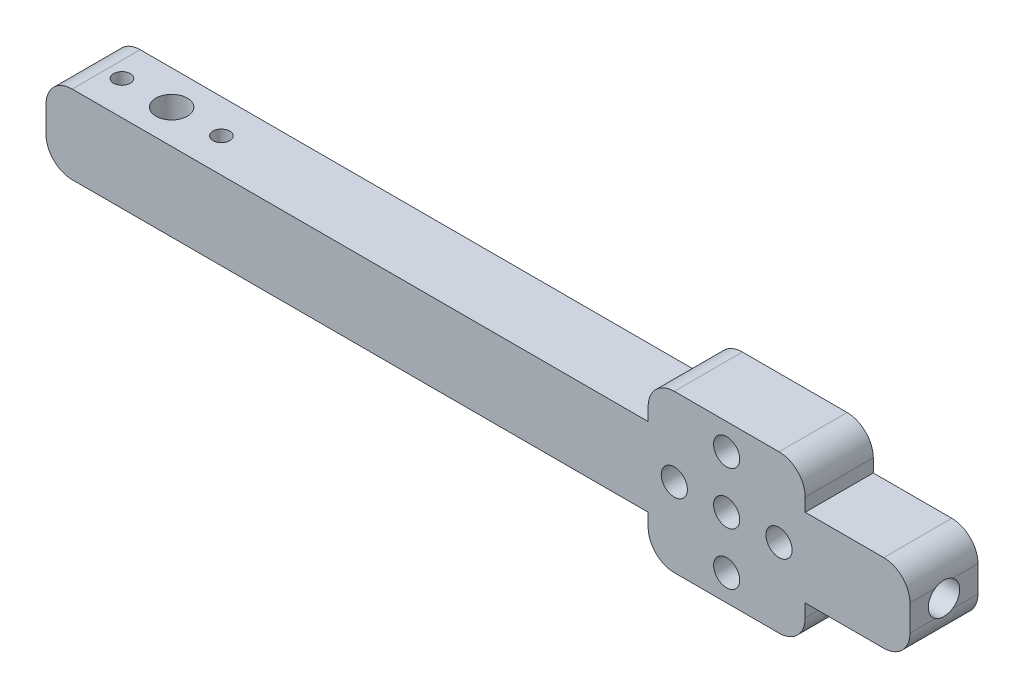
SolidWorks part; units mm, degrees
ref_plane "Front Plane" through (0, 0, 0) normal (0, 0, 1) x (1, 0, 0)
ref_plane "Top Plane" through (0, 0, 0) normal (0, 1, 0) x (1, 0, 0)
ref_plane "Right Plane" through (0, 0, 0) normal (1, 0, 0) x (0, 0, -1)
sketch "Sketch1" plane through (0, 0, 0) normal (1, 0, 0) x (0, 0, -1)
  line L1 (-6.5, -7.5) -> (6.5, -7.5)
  line L2 (-6.5, -7.5) -> (-6.5, 7.5)
  line L3 (-6.5, 7.5) -> (6.5, 7.5)
  line L4 (6.5, -7.5) -> (6.5, 7.5)
  line L5 (-6.5, -7.5) -> (6.5, 7.5) construction
  line L6 (-6.5, 7.5) -> (6.5, -7.5) construction
  point P0 (0, 0)
  dimension "D1" = 13
  dimension "D2" = 15
extrude "Boss-Extrude1" add sketch "Sketch1" along normal blind 150
sketch "Sketch5" plane through (0, 0, 6.5) normal (0, 0, 1) x (1, 0, 0)
  line L0 (115, 7.5) -> (115, -7.5)
  line L1 (150, 7.5) -> (0, 7.5) construction
  line L2 (150, -7.5) -> (0, -7.5) construction
  line L4 (0, 7.5) -> (0, -7.5) construction
  circle A0 centre (115, 0) radius 2.5
  circle A1 centre (125, 0) radius 2.5
  circle A2 centre (105, 0) radius 2.5
  dimension "D1" = 5
  dimension "D3" = 10
  dimension "D4" = 10
  dimension "D5" = 5
  dimension "D6" = 5
  dimension "D2" = 115
extrude "Cut-Extrude3" cut sketch "Sketch5" against normal through all contours A2 | A0 | A1
sketch "Sketch8" plane through (0, 0, 0) normal (-1, 0, 0) x (0, 0, 1)
  line L1 (-6.5, 7.5) -> (6.5, 7.5)
  line L2 (-6.5, 7.5) -> (-6.5, -7.5)
  line L3 (-6.5, -7.5) -> (6.5, -7.5)
  line L4 (6.5, 7.5) -> (6.5, -7.5)
extrude "Boss-Extrude3" add sketch "Sketch8" along normal blind 15
sketch "Sketch10" plane through (0, -7.5, 0) normal (0, -1, 0) x (-1, 0, 0)
  line L0 (-150, -6.5) -> (15, -6.5) construction
  line L1 (15, 6.5) -> (-15, 6.5)
  line L2 (15, 6.5) -> (15, -6.5)
  line L3 (15, -6.5) -> (-15, -6.5)
  line L4 (-15, 6.5) -> (-15, -6.5)
  line L5 (15, 6.5) -> (-15, -6.5) construction
  line L6 (15, -6.5) -> (-15, 6.5) construction
  line L7 (15, 6.5) -> (15, -6.5) construction
  line L8 (15, 0) -> (-15, 0)
  circle A0 centre (7, 0) radius 1.6
  circle A1 centre (-12, 0) radius 1.6
  point P0 (0, 0)
  dimension "D3" = 3.2
  dimension "D4" = 3.2
  dimension "D5" = 8
  dimension "D6" = 3
  dimension "D1" = 15
  dimension "D2" = 30
extrude "Cut-Extrude4" cut sketch "Sketch10" against normal through all contours A0 | A1
sketch "Sketch11" plane through (0, 0, -6.5) normal (0, 0, -1) x (-1, 0, 0)
  line L1 (-130, -15) -> (-100, -15)
  line L2 (-130, -15) -> (-130, 15)
  line L3 (-130, 15) -> (-100, 15)
  line L4 (-100, -15) -> (-100, 15)
  line L5 (-130, -15) -> (-100, 15) construction
  line L6 (-130, 15) -> (-100, -15) construction
  point P0 (-115, 0)
  dimension "D1" = 30
  dimension "D2" = 30
extrude "Boss-Extrude4" add sketch "Sketch11" against normal blind 13
sketch "Sketch12" plane through (0, 0, -6.5) normal (0, 0, -1) x (-1, 0, 0)
  line L0 (-115, 7.5) -> (-115, -7.5) construction
  line L1 (-115, 7.5) -> (-115, -7.5)
  circle A0 centre (-115, 10) radius 2.5
  circle A1 centre (-105, 0) radius 2.5
  circle A2 centre (-105, 0) radius 2.5
  circle A3 centre (-125, 0) radius 2.5
  circle A4 centre (-125, 0) radius 2.5
  circle A5 centre (-115, 0) radius 2.5
  circle A6 centre (-115, 0) radius 2.5
  circle A7 centre (-115, -10) radius 2.5
  dimension "D4" = 10
  dimension "D5" = 10
  dimension "D6" = 5
  dimension "D7" = 5
  dimension "D1" = 0
  dimension "D2" = 0
  dimension "D3" = 0
extrude "Cut-Extrude5" cut sketch "Sketch12" against normal through all contours A0 | A4 | A6 | A2 | A7
fillet "Fillet1" radius 5 4 edges at (130, -15, 0) (100, -15, 0) (100, 15, 0) (130, 15, 0)
fillet "Fillet2" radius 5 4 edges at (-15, -7.5, 0) (-15, 7.5, 0) (150, -7.5, 0) (150, 7.5, 0)
sketch "Sketch13" plane through (0, 7.5, 0) normal (0, 1, 0) x (1, 0, 0)
  circle A1 centre (2.5, 0) radius 3
  circle A2 centre (-7, 0) radius 1.6 construction
  dimension "D1" = 6
  dimension "D2" = 9.5
extrude "Cut-Extrude6" cut sketch "Sketch13" against normal through all
sketch "Sketch14" plane through (150, 0, 0) normal (1, 0, 0) x (0, 0, -1)
  line L0 (-6.5, 2.5) -> (-6.5, -2.5) construction
  line L1 (6.5, -2.5) -> (6.5, 2.5) construction
  circle A0 centre (0, 0) radius 3
  dimension "D1" = 6
  dimension "D2" = 6.5
  dimension "D3" = 6.5
extrude "Cut-Extrude7" cut sketch "Sketch14" against normal blind 150
